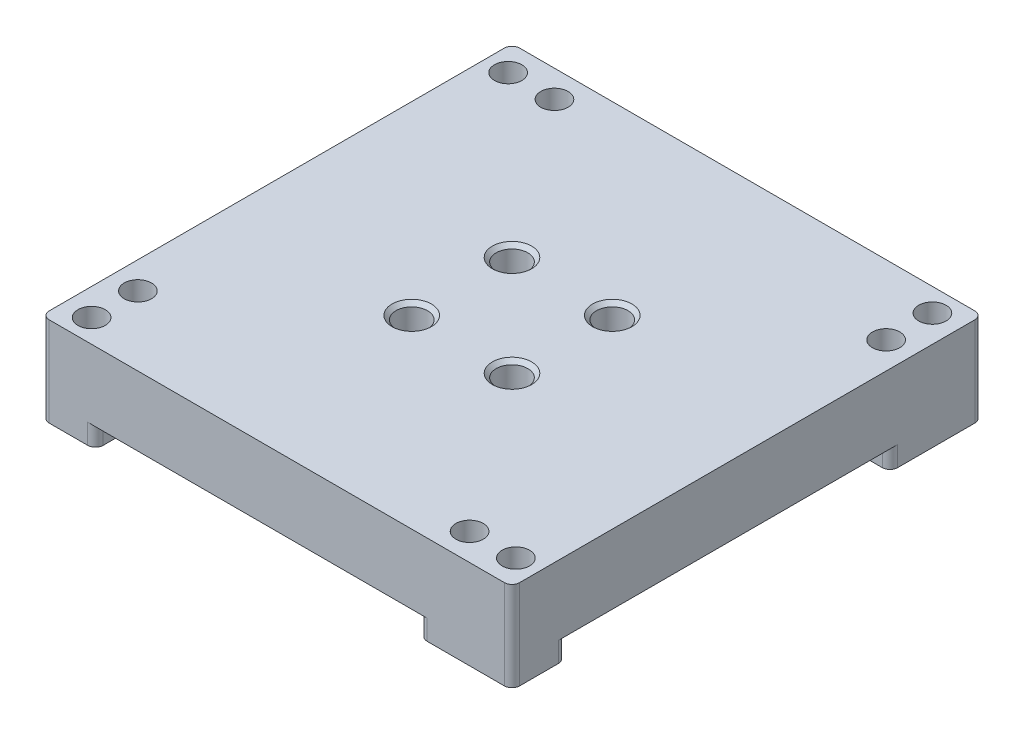
SolidWorks part; units mm, degrees
ref_plane "Front Plane" through (0, 0, 0) normal (0, 0, 1) x (1, 0, 0)
ref_plane "Top Plane" through (0, 0, 0) normal (0, 1, 0) x (1, 0, 0)
ref_plane "Right Plane" through (0, 0, 0) normal (1, 0, 0) x (0, 0, -1)
sketch "Sketch1" plane through (0, 0, 0) normal (0, 1, 0) x (1, 0, 0)
  line L1 (28.5, -30.5) -> (-28.5, -30.5)
  line L2 (30.5, -28.5) -> (30.5, 28.5)
  line L3 (28.5, 30.5) -> (-28.5, 30.5)
  line L4 (-30.5, -28.5) -> (-30.5, 28.5)
  line L5 (30.5, -30.5) -> (-30.5, 30.5) construction
  line L6 (30.5, 30.5) -> (-30.5, -30.5) construction
  arc A0 (28.5, -30.5) -> (30.5, -28.5) centre (28.5, -28.5) ccw
  arc A1 (-28.5, -30.5) -> (-30.5, -28.5) centre (-28.5, -28.5) cw
  arc A2 (30.5, 28.5) -> (28.5, 30.5) centre (28.5, 28.5) ccw
  arc A3 (-28.5, 30.5) -> (-30.5, 28.5) centre (-28.5, 28.5) ccw
  point P0 (0, 0)
  dimension "D3" = 2
  dimension "D1" = 61
  dimension "D2" = 61
extrude "Boss-Extrude1" add sketch "Sketch1" along normal blind 9
sketch "Sketch2" plane through (0, 9, 0) normal (0, 1, 0) x (1, 0, 0)
  line L0 (-27, -21.5) -> (-27, -27.5) construction
  line L2 (30.5, -30.5) -> (30.5, 30.5) construction
  line L3 (30.5, 30.5) -> (-30.5, 30.5) construction
  line L5 (30.5, -30.5) -> (-30.5, 30.5) construction
  line L6 (30.5, 30.5) -> (-30.5, -30.5) construction
  line L15 (-30.5, -30.5) -> (-23.5, -30.5)
  line L16 (-30.5, -30.5) -> (-30.5, -18.5)
  line L17 (-30.5, -18.5) -> (-23.5, -18.5)
  line L18 (-23.5, -30.5) -> (-23.5, -18.5)
  line L23 (21.5, -27) -> (27.5, -27) construction
  line L24 (30.5, -30.5) -> (18.5, -30.5)
  line L25 (30.5, -30.5) -> (30.5, -23.5)
  line L26 (30.5, -23.5) -> (18.5, -23.5)
  line L27 (18.5, -30.5) -> (18.5, -23.5)
  line L28 (-30.5, 30.5) -> (-30.5, -30.5) construction
  line L29 (30.5, -30.5) -> (-30.5, -30.5) construction
  line L30 (30.5, 30.5) -> (23.5, 30.5)
  line L31 (30.5, 30.5) -> (30.5, 18.5)
  line L32 (30.5, 18.5) -> (23.5, 18.5)
  line L33 (23.5, 30.5) -> (23.5, 18.5)
  line L34 (-30.5, 30.5) -> (-18.5, 30.5)
  line L35 (-30.5, 30.5) -> (-30.5, 23.5)
  line L36 (-30.5, 23.5) -> (-18.5, 23.5)
  line L37 (-18.5, 30.5) -> (-18.5, 23.5)
  line L38 (27, 21.5) -> (27, 27.5) construction
  line L39 (-21.5, 27) -> (-27.5, 27) construction
  circle A0 centre (-27, -21.5) radius 1.775
  circle A1 centre (-27, -27.5) radius 1.775
  circle A4 centre (21.5, -27) radius 1.775
  circle A5 centre (27.5, -27) radius 1.775
  circle A6 centre (27, 21.5) radius 1.775
  circle A7 centre (27, 27.5) radius 1.775
  circle A8 centre (-21.5, 27) radius 1.775
  circle A9 centre (-27.5, 27) radius 1.775
  point P0 (0, 0)
  point P14 (-27, -18.5)
  point P22 (24.5, -27)
  point P23 (24.5, -23.5)
  point P29 (30.5, -27)
  point P42 (0, 0)
  dimension "D8" = 3.55
  dimension "D12" = 3.55
  dimension "D1" = 61
  dimension "62" = 61
  dimension "D3" = 7
  dimension "D4" = 12
  dimension "D5" = 6
  dimension "D6" = 3
  dimension "D7" = 3
  dimension "D9" = 12
  dimension "D10" = 7
  dimension "D11" = 6
  dimension "D13" = 3.5
  dimension "D14" = 3
  dimension "D15" = 2
extrude "Boss-Extrude2" add sketch "Sketch2" against normal blind 11.6
sketch "Sketch7" plane through (0, 9, 0) normal (0, 1, 0) x (1, 0, 0)
  circle A0 centre (27.5, -27) radius 1.775 construction
  circle A1 centre (21.5, -27) radius 1.775 construction
  circle A2 centre (-27, -27.5) radius 1.775 construction
  circle A3 centre (-27, -21.5) radius 1.775 construction
  circle A4 centre (27, 21.5) radius 1.775 construction
  circle A5 centre (27, 27.5) radius 1.775 construction
  circle A6 centre (-21.5, 27) radius 1.775 construction
  circle A7 centre (-27.5, 27) radius 1.775 construction
  circle A8 centre (27.5, -27) radius 1.775
  circle A9 centre (21.5, -27) radius 1.775
  circle A10 centre (-27, -27.5) radius 1.775
  circle A11 centre (-27, -21.5) radius 1.775
  circle A12 centre (27, 21.5) radius 1.775
  circle A13 centre (27, 27.5) radius 1.775
  circle A14 centre (-21.5, 27) radius 1.775
  circle A15 centre (-27.5, 27) radius 1.775
extrude "Cut-Extrude1" cut sketch "Sketch7" against normal through all
sketch "Sketch8" plane through (0, 0, 0) normal (0, -1, 0) x (1, 0, 0)
  line L0 (-27, 27.5) -> (-27, 21.5) construction
  line L1 (-23.6, 27.5) -> (-23.6, 21.5)
  line L2 (-30.4, 27.5) -> (-30.4, 21.5)
  line L3 (-27.5, -27) -> (-21.5, -27) construction
  line L4 (-27.5, -23.6) -> (-21.5, -23.6)
  line L5 (-27.5, -30.4) -> (-21.5, -30.4)
  line L6 (21.5, 27) -> (27.5, 27) construction
  line L7 (21.5, 30.4) -> (27.5, 30.4)
  line L8 (21.5, 23.6) -> (27.5, 23.6)
  line L9 (27, -21.5) -> (27, -27.5) construction
  line L10 (30.4, -21.5) -> (30.4, -27.5)
  line L11 (23.6, -21.5) -> (23.6, -27.5)
  arc A0 (-23.6, 27.5) -> (-30.4, 27.5) centre (-27, 27.5) ccw
  arc A1 (-30.4, 21.5) -> (-23.6, 21.5) centre (-27, 21.5) ccw
  arc A2 (-27.5, -23.6) -> (-27.5, -30.4) centre (-27.5, -27) ccw
  arc A3 (-21.5, -30.4) -> (-21.5, -23.6) centre (-21.5, -27) ccw
  arc A4 (21.5, 30.4) -> (21.5, 23.6) centre (21.5, 27) ccw
  arc A5 (27.5, 23.6) -> (27.5, 30.4) centre (27.5, 27) ccw
  arc A6 (30.4, -21.5) -> (23.6, -21.5) centre (27, -21.5) ccw
  arc A7 (23.6, -27.5) -> (30.4, -27.5) centre (27, -27.5) ccw
  point P4 (-27, 24.5)
  point P9 (-24.5, -27)
  point P22 (24.5, 27)
  point P27 (27, -24.5)
  dimension "D1" = 3.4
  dimension "D2" = 3.4
  dimension "D3" = 3.4
  dimension "D4" = 3.4
fillet "Fillet1" radius 1 16 edges at (-30.5, -1.3, 18.5) (30.5, -1.3, 23.5) (18.5, -1.3, 23.5) (30.5, 3.2, 30.5) (18.5, -1.3, 30.5) (-23.5, -1.3, 18.5) (-30.5, 3.2, 30.5) (-23.5, -1.3, 30.5) (30.5, 3.2, -30.5) (23.5, -1.3, -30.5) (23.5, -1.3, -18.5) (30.5, -1.3, -18.5) (-18.5, -1.3, -30.5) (-30.5, -1.3, -23.5) (-18.5, -1.3, -23.5) (-30.5, 3.2, -30.5)
sketch "Sketch11" plane through (0, 9, 0) normal (0, 1, 0) x (1, 0, 0)
  line L0 (29.5, 30.5) -> (-29.5, 30.5) construction
  line L3 (-18.6, 23.5) -> (-30.5, 23.5)
  line L6 (-18.6, 23.5) -> (-18.6, 30.5)
  line L9 (-18.6, 30.5) -> (-30.5, 30.5)
  line L12 (-30.5, 23.5) -> (-30.5, 30.5)
  line L13 (-18.6, 23.5) -> (-30.5, 30.5) construction
  line L14 (-18.6, 30.5) -> (-30.5, 23.5) construction
  line L15 (-30.5, 29.5) -> (-30.5, -29.5) construction
  line L16 (23.5, 18.6) -> (23.5, 30.5)
  line L17 (23.5, 18.6) -> (30.5, 18.6)
  line L18 (30.5, 18.6) -> (30.5, 30.5)
  line L19 (23.5, 30.5) -> (30.5, 30.5)
  line L20 (23.5, 18.6) -> (30.5, 30.5) construction
  line L21 (30.5, 18.6) -> (23.5, 30.5) construction
  line L22 (18.6, -23.5) -> (30.5, -23.5)
  line L23 (18.6, -23.5) -> (18.6, -30.5)
  line L24 (18.6, -30.5) -> (30.5, -30.5)
  line L25 (30.5, -23.5) -> (30.5, -30.5)
  line L26 (18.6, -23.5) -> (30.5, -30.5) construction
  line L27 (18.6, -30.5) -> (30.5, -23.5) construction
  line L28 (-23.5, -18.6) -> (-23.5, -30.5)
  line L29 (-23.5, -18.6) -> (-30.5, -18.6)
  line L30 (-30.5, -18.6) -> (-30.5, -30.5)
  line L31 (-23.5, -30.5) -> (-30.5, -30.5)
  line L32 (-23.5, -18.6) -> (-30.5, -30.5) construction
  line L33 (-30.5, -18.6) -> (-23.5, -30.5) construction
  circle A8 centre (-21.5, 27) radius 2.9 construction
  circle A9 centre (27, 21.5) radius 2.9 construction
  circle A10 centre (21.5, -27) radius 2.9 construction
  circle A11 centre (-27, -21.5) radius 2.9 construction
  point P8 (-24.55, 27)
  point P20 (27, 24.55)
  point P27 (24.55, -27)
  point P34 (-27, -24.55)
  point P35 (0, 0)
  dimension "D1" = 5.8
  dimension "D3" = 3.5
  dimension "D2" = 0.6
  dimension "D4" = 4
extrude "Cut-Extrude4" [suppressed] cut sketch "Sketch11" against normal blind 2.6
sketch "Sketch15" plane through (0, 0, 0) normal (0, -1, 0) x (1, 0, 0)
  line L0 (17.8, -7.6) -> (-17.8, -7.6) construction
  line L1 (17.8, -7.6) -> (17.8, 7.6) construction
  line L2 (17.8, 7.6) -> (-17.8, 7.6) construction
  line L3 (-17.8, -7.6) -> (-17.8, 7.6) construction
  line L4 (17.8, -7.6) -> (-17.8, 7.6) construction
  line L5 (17.8, 7.6) -> (-17.8, -7.6) construction
  circle A0 centre (-17.8, 7.6) radius 1.65
  circle A1 centre (17.8, 7.6) radius 1.6
  circle A2 centre (-17.8, -7.6) radius 1.65
  circle A3 centre (17.8, -7.6) radius 1.6
  point P0 (0, 0)
  dimension "D3" = 3.3
  dimension "D4" = 3.2
  dimension "D1" = 35.6
  dimension "D2" = 15.2
sketch "Sketch16" plane through (0, 0, 0) normal (0, -1, 0) x (1, 0, 0)
  line L0 (17.8, -7.6) -> (-17.8, -7.6) construction
  line L1 (17.8, -7.6) -> (17.8, 7.6) construction
  line L2 (17.8, 7.6) -> (-17.8, 7.6) construction
  line L3 (-17.8, -7.6) -> (-17.8, 7.6) construction
  line L4 (17.8, -7.6) -> (-17.8, 7.6) construction
  line L5 (17.8, 7.6) -> (-17.8, -7.6) construction
  circle A0 centre (-17.8, 7.6) radius 1.65
  circle A1 centre (17.8, 7.6) radius 1.6
  circle A2 centre (-17.8, -7.6) radius 1.65
  circle A3 centre (17.8, -7.6) radius 1.6
  point P0 (0, 0)
  dimension "D3" = 3.3
  dimension "D4" = 3.2
  dimension "D1" = 35.6
  dimension "D2" = 15.2
sketch "Sketch17" plane through (0, 9, 0) normal (0, 1, 0) x (1, 0, 0)
  line L1 (6.5, -6.5) -> (-6.5, -6.5) construction
  line L2 (6.5, -6.5) -> (6.5, 6.5) construction
  line L3 (6.5, 6.5) -> (-6.5, 6.5) construction
  line L4 (-6.5, -6.5) -> (-6.5, 6.5) construction
  line L5 (6.5, -6.5) -> (-6.5, 6.5) construction
  line L6 (6.5, 6.5) -> (-6.5, -6.5) construction
  circle A0 centre (-6.5, 6.5) radius 2.05
  circle A1 centre (6.5, 6.5) radius 2.05
  circle A2 centre (-6.5, -6.5) radius 2.05
  circle A3 centre (6.5, -6.5) radius 2.05
  point P0 (0, 0)
  dimension "D3" = 4.1
  dimension "D1" = 13
  dimension "D2" = 13
extrude "Cut-Extrude9" cut sketch "Sketch17" against normal blind 6.5
sketch "Sketch18" plane through (0, 0, 30.5) normal (0, 0, 1) x (1, 0, 0)
  line L0 (-14.66, 3.29) -> (5.66, 3.29) construction
  line L1 (-30.5, -2.6) -> (-30.5, 9) construction
  line L3 (-24.5, 0) -> (19.5, 0) construction
  circle A0 centre (-14.66, 3.29) radius 1.725
  circle A1 centre (5.66, 3.29) radius 1.725
  point P2 (-4.5, 3.29)
  dimension "D1" = 3.45
  dimension "D2" = 20.32
  dimension "D3" = 26
  dimension "D4" = 3.29
chamfer "Chamfer1" distance 0.5 angle 45 4 edges at (6.5, 9, 8.55) (-6.5, 9, 8.55) (6.5, 9, -4.45) (-6.5, 9, -4.45)
equation "\"D9@Sketch2\"=\"D4@Sketch2\""
equation "\"D10@Sketch2\"=\"D3@Sketch2\""
equation "\"D12@Sketch2\"=\"D8@Sketch2\""
equation "\"D14@Sketch2\"=\"D6@Sketch2\""
equation "\"D11@Sketch2\"=\"D5@Sketch2\""
equation "\"D2@Sketch8\"=\"D1@Sketch8\""
equation "\"D3@Sketch8\"=\"D1@Sketch8\""
equation "\"D4@Sketch8\"=\"D1@Sketch8\""
